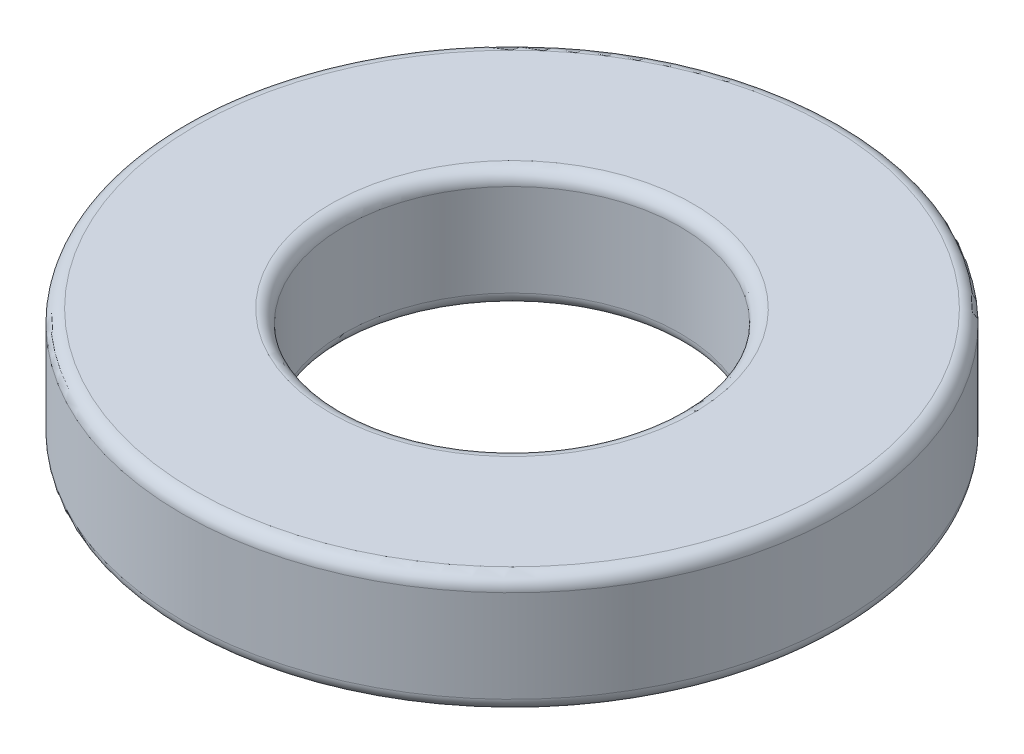
SolidWorks part; units mm, degrees
ref_plane "Front Plane" through (0, 0, 0) normal (0, 0, 1) x (1, 0, 0)
ref_plane "Top Plane" through (0, 0, 0) normal (0, 1, 0) x (1, 0, 0)
ref_plane "Right Plane" through (0, 0, 0) normal (1, 0, 0) x (0, 0, -1)
sketch "Sketch1" plane through (0, 0, 0) normal (0, 1, 0) x (1, 0, 0)
  circle A0 centre (0, 0) radius 25
  circle A1 centre (0, 0) radius 12.75
  dimension "D1" = 50
  dimension "D2" = 25.5
extrude "Boss-Extrude1" add sketch "Sketch1" along normal blind 9
fillet "Fillet1" radius 1 4 edges at (0, 0, 25) (0, 9, 25) (0, 0, 12.75) (0, 9, 12.75)
